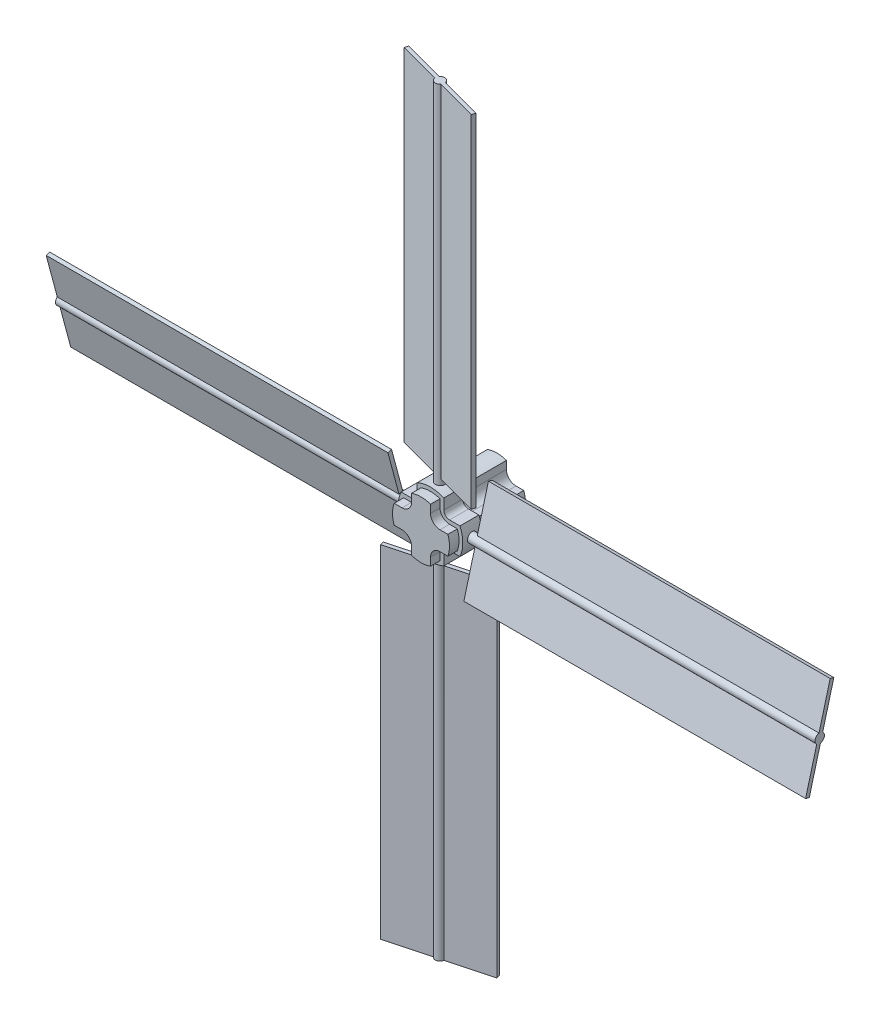
SolidWorks part; units mm, degrees
note: '?' marks a value the reader was unsure of. The reader was unsure of these and kept them because the rebuilt part matched: shared geometry of "Sketch3<3>".
ref_plane "Front Plane" through (0, 0, 0) normal (1, 0, 0) x (0, 1, 0)
ref_plane "Top Plane" through (0, 0, 0) normal (0, 0, 1) x (0, 1, 0)
ref_plane "Right Plane" through (0, 0, 0) normal (0, 1, 0) x (-1, 0, 0)
sketch "Sketch1" plane through (0, 0, 0) normal (0, 0, 1) x (0, 1, 0)
  line L1 (-50, 141.4214) -> (-50, 0)
  line L2 (50, 141.4214) -> (50, 0)
  line L3 (-50, 0) -> (50, 0)
  arc A0 (50, 141.4214) -> (-50, 141.4214) centre (0, 0) ccw
  point P1 (-46.9864, 140.328)
  point P3 (0, 0)
  point P6 (50, 0)
  point P9 (-50, -34.7177)
  dimension "D1" = 150
  dimension "D2" = 100
extrude "Boss-Extrude1" add sketch "Sketch1" along normal blind 400
ref_axis "Axis1" through (0, 0, -10) along (0, 0, 1)?
pattern_circular "CirPattern1" count 4 over 360 about axis through (0, 0, 0) along (0, 0, 1) of bodies 101
combine bodies "Combine1" bodies to combine 101 102 103 104
fillet "Fillet1" radius 50 4 edges at (-50, 50, 200) (-50, -50, 200) (50, -50, 200) (50, 50, 200)
sketch "Sketch2" plane through (0, 0, 400) normal (0, 0, 1) x (1, 0, 0)
  line L0 (-70, 154.9193) -> (-70, 100)
  line L1 (-100, 70) -> (-154.9193, 70)
  line L2 (-154.9193, -70) -> (-100, -70)
  line L3 (-70, -100) -> (-70, -154.9193)
  line L4 (70, -154.9193) -> (70, -100)
  line L5 (100, -70) -> (154.9193, -70)
  line L6 (154.9193, 70) -> (100, 70)
  line L7 (70, 100) -> (70, 154.9193)
  line L8 (-50, 141.4214) -> (-50, 100)
  line L9 (-100, 50) -> (-141.4214, 50)
  line L10 (-141.4214, -50) -> (-100, -50)
  line L11 (-50, -100) -> (-50, -141.4214)
  line L12 (50, -141.4214) -> (50, -100)
  line L13 (100, -50) -> (141.4214, -50)
  line L14 (141.4214, 50) -> (100, 50)
  line L15 (50, 100) -> (50, 141.4214)
  line L16 (-50, 141.4214) -> (-50, 100) construction
  line L17 (-100, 50) -> (-141.4214, 50) construction
  line L18 (-141.4214, -50) -> (-100, -50) construction
  line L19 (-50, -100) -> (-50, -141.4214) construction
  line L20 (50, -141.4214) -> (50, -100) construction
  line L21 (100, -50) -> (141.4214, -50) construction
  line L22 (141.4214, 50) -> (100, 50) construction
  line L23 (50, 100) -> (50, 141.4214) construction
  arc A1 (-100, 70) -> (-70, 100) centre (-100, 100) ccw
  arc A2 (-154.9193, 70) -> (-154.9193, -70) centre (0, 0) ccw
  arc A3 (-70, -100) -> (-100, -70) centre (-100, -100) ccw
  arc A4 (-70, -154.9193) -> (70, -154.9193) centre (0, 0) ccw
  arc A5 (100, -70) -> (70, -100) centre (100, -100) ccw
  arc A6 (154.9193, -70) -> (154.9193, 70) centre (0, 0) ccw
  arc A7 (70, 100) -> (100, 70) centre (100, 100) ccw
  arc A8 (70, 154.9193) -> (-70, 154.9193) centre (0, 0) ccw
  arc A9 (-100, 50) -> (-50, 100) centre (-100, 100) ccw
  arc A10 (-141.4214, 50) -> (-141.4214, -50) centre (0, 0) ccw
  arc A11 (-50, -100) -> (-100, -50) centre (-100, -100) ccw
  arc A12 (-50, -141.4214) -> (50, -141.4214) centre (0, 0) ccw
  arc A13 (100, -50) -> (50, -100) centre (100, -100) ccw
  arc A14 (141.4214, -50) -> (141.4214, 50) centre (0, 0) ccw
  arc A15 (50, 100) -> (100, 50) centre (100, 100) ccw
  arc A16 (50, 141.4214) -> (-50, 141.4214) centre (0, 0) ccw
  arc A17 (-100, 50) -> (-50, 100) centre (-100, 100) ccw construction
  arc A18 (-141.4214, 50) -> (-141.4214, -50) centre (0, 0) ccw construction
  arc A19 (-50, -100) -> (-100, -50) centre (-100, -100) ccw construction
  arc A20 (-50, -141.4214) -> (50, -141.4214) centre (0, 0) ccw construction
  arc A21 (100, -50) -> (50, -100) centre (100, -100) ccw construction
  arc A22 (141.4214, -50) -> (141.4214, 50) centre (0, 0) ccw construction
  arc A23 (50, 100) -> (100, 50) centre (100, 100) ccw construction
  arc A24 (50, 141.4214) -> (-50, 141.4214) centre (0, 0) ccw construction
  dimension "D1" = 0
  dimension "D2" = 20
extrude "Boss-Extrude2" add sketch "Sketch2" against normal blind 100 from offset 50 offset against normal yes
sketch "Sketch3" plane through (0, 0, 0) normal (0, 1, 0) x (-1, 0, 0)
  line L0 (-70, 250) -> (-70, 350) construction
  line L2 (-70, 250) -> (-70, 350) construction
  line L3 (-241.4815, 364.7048) -> (241.4815, 235.2952)
  circle A0 centre (0, 300) radius 25
  point P4 (0, 300)
  point P5 (-70, 300)
  point P8 (-488.121, 429.4095)
  point P9 (0, 0)
  dimension "D1" = 50
  dimension "D2" = 15
  dimension "D3" = 500
extrude "Boss-Extrude3" add sketch "Sketch3" along normal blind 2000 separate body contours A0
extrude "Extrude-Thin1" add sketch "Sketch3<3>" along normal up to surface (1800 mm away) from offset 200 thin contours L3
sketch "Sketch3<3>" plane through (0, 0, 0) normal (0, 1, 0) x (-1, 0, 0) same geometry as "Sketch3"
pattern_circular "CirPattern2" count 4 over 360 about axis through (0, 0, 0) along (0, 0, 1) of bodies 108
combine bodies "Combine2" bodies to combine 106 108 109 110 111
